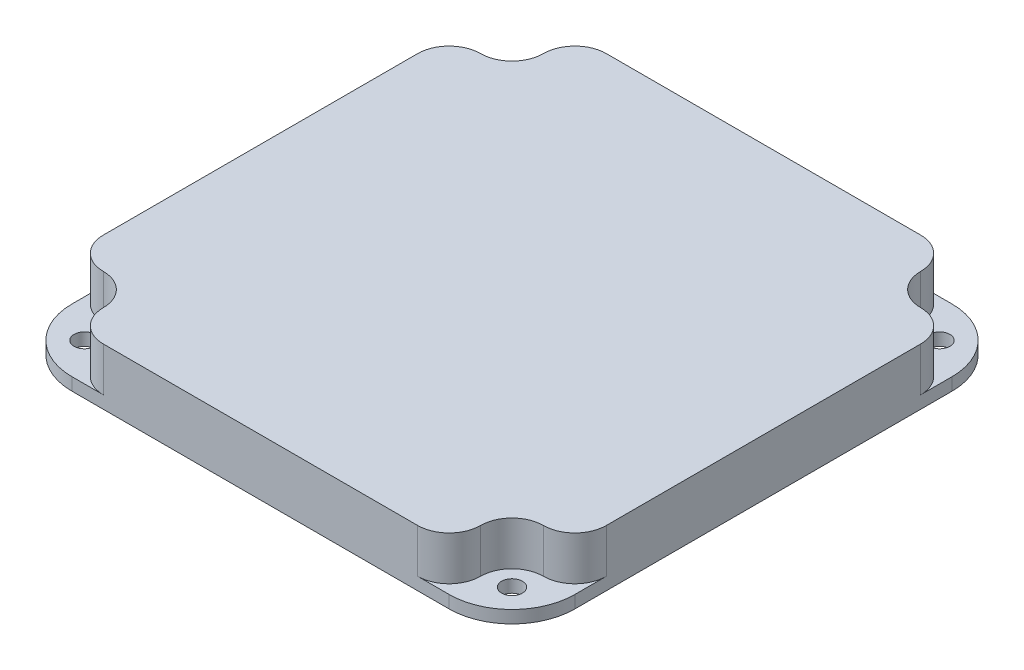
SolidWorks part; units mm, degrees
ref_plane "前视基准面" through (0, 0, 0) normal (0, 0, 1) x (1, 0, 0)
ref_plane "上视基准面" through (0, 0, 0) normal (0, 1, 0) x (1, 0, 0)
ref_plane "右视基准面" through (0, 0, 0) normal (1, 0, 0) x (0, 0, -1)
sketch "草图1" plane through (0, 0, 0) normal (0, 1, 0) x (1, 0, 0)
  line L0 (0, 0) -> (0, -9.1145) construction
  line L1 (-30, -40) -> (30, -40)
  line L2 (-40, -30) -> (-40, 30)
  line L3 (-30, 40) -> (30, 40)
  line L4 (40, -30) -> (40, 30)
  line L5 (-40, -40) -> (40, 40) construction
  line L6 (-40, 40) -> (40, -40) construction
  line L7 (0, 0) -> (7.0842, 0) construction
  circle A0 centre (-34, 34) radius 1.65
  arc A1 (-40, 30) -> (-30, 40) centre (-30, 30) cw
  arc A2 (-30, -40) -> (-40, -30) centre (-30, -30) cw
  arc A3 (30, -40) -> (40, -30) centre (30, -30) ccw
  arc A4 (30, 40) -> (40, 30) centre (30, 30) cw
  circle A5 centre (-34, -34) radius 1.65
  circle A6 centre (34, 34) radius 1.65
  circle A7 centre (34, -34) radius 1.65
  point P0 (0, 0)
  dimension "D3" = 3.3
  dimension "D6" = 10
  dimension "D7" = 10
  dimension "D1" = 80
  dimension "D2" = 80
  dimension "D4" = 6
  dimension "D5" = 6
extrude "凸台-拉伸1" add sketch "草图1" along normal blind 2
sketch "草图2" plane through (0, 2, 0) normal (0, 1, 0) x (1, 0, 0)
  line L0 (-30, 40) -> (-30, 30)
  line L1 (-30, 30) -> (-40, 30)
  line L2 (-40, 30) -> (-40, -30)
  line L3 (-40, -30) -> (-30, -30)
  line L4 (-30, -30) -> (-30, -40)
  line L5 (-30, -40) -> (30, -40)
  line L6 (30, -40) -> (30, -30)
  line L7 (30, -30) -> (40, -30)
  line L8 (40, -30) -> (40, 30)
  line L9 (40, 30) -> (30, 30)
  line L10 (30, 30) -> (30, 40)
  line L11 (30, 40) -> (-30, 40)
extrude "凸台-拉伸2" add sketch "草图2" along normal blind 7
fillet "圆角1" radius 5 12 edges at (-40, 5.5, -30) (-30, 5.5, -30) (-30, 5.5, -40) (30, 5.5, -40) (30, 5.5, -30) (40, 5.5, -30) (40, 5.5, 30) (30, 5.5, 30) (30, 5.5, 40) (-40, 5.5, 30) (-30, 5.5, 30) (-30, 5.5, 40)
